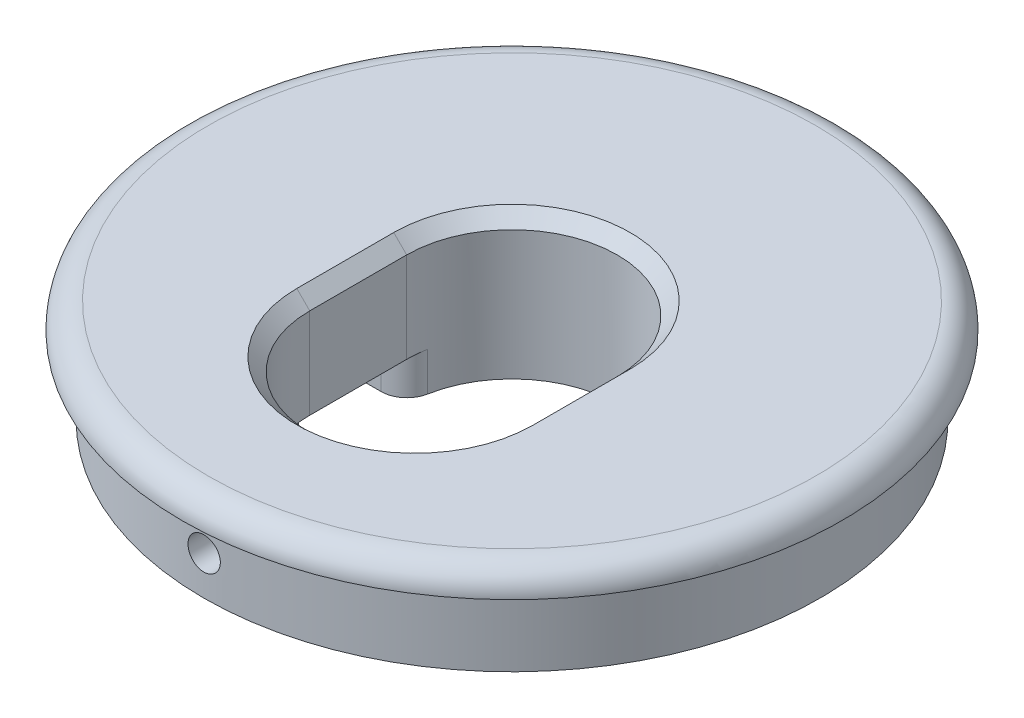
SolidWorks part; units mm, degrees
ref_plane "Front Plane" through (0, 0, 0) normal (0, 0, 1) x (1, 0, 0)
ref_plane "Top Plane" through (0, 0, 0) normal (0, 1, 0) x (1, 0, 0)
ref_plane "Right Plane" through (0, 0, 0) normal (1, 0, 0) x (0, 0, -1)
sketch "Sketch1" plane through (0, 0, 0) normal (0, 1, 0) x (1, 0, 0)
  circle A0 centre (0, 0) radius 23.85
  dimension "D1" = 47.7
extrude "Boss-Extrude1" add sketch "Sketch1" along normal blind 6
sketch "Sketch2" plane through (0, 6, 0) normal (0, 1, 0) x (1, 0, 0)
  circle A0 centre (0, 0) radius 25.5
  dimension "D1" = 51
extrude "Boss-Extrude2" add sketch "Sketch2" along normal blind 2
fillet "Fillet1" radius 2 1 edges at (0, 8, 25.5)
sketch "Sketch3" plane through (0, 8, 0) normal (0, 1, 0) x (1, 0, 0)
  line L0 (0, 0) -> (0, -7.5) construction
  line L1 (8.15, 0) -> (8.15, -7.5)
  line L2 (-8.15, 0) -> (-8.15, -7.5)
  arc A0 (8.15, 0) -> (-8.15, 0) centre (0, 0) ccw
  arc A1 (-8.15, -7.5) -> (8.15, -7.5) centre (0, -7.5) ccw
  point P3 (0, -3.75)
  dimension "D2" = 8.15
  dimension "D1" = 7.5
extrude "Cut-Extrude1" cut sketch "Sketch3" against normal through all
sketch "Sketch4" plane through (0, 0, 0) normal (0, -1, 0) x (1, 0, 0)
  line L0 (-12.15, 7.5) -> (-12.15, 0)
  line L1 (12.15, 0) -> (12.15, 7.5)
  line L2 (8.15, 0) -> (8.15, 7.5)
  line L3 (-8.15, 7.5) -> (-8.15, 0)
  line L4 (8.15, 0) -> (8.15, 7.5)
  line L5 (-8.15, 7.5) -> (-8.15, 0)
  arc A0 (12.15, 7.5) -> (-12.15, 7.5) centre (0, 7.5) ccw
  arc A1 (-12.15, 0) -> (12.15, 0) centre (0, 0) ccw
  arc A2 (-8.15, 0) -> (8.15, 0) centre (0, 0) ccw
  arc A3 (8.15, 7.5) -> (-8.15, 7.5) centre (0, 7.5) ccw
  arc A4 (-8.15, 0) -> (8.15, 0) centre (0, 0) ccw
  arc A5 (8.15, 7.5) -> (-8.15, 7.5) centre (0, 7.5) ccw
  dimension "D1" = 0
  dimension "D2" = 4
extrude "Boss-Extrude3" add sketch "Sketch4" along normal blind 3
sketch "Sketch5" plane through (0, -3, 0) normal (0, -1, 0) x (1, 0, 0)
  line L0 (0, 3.75) -> (0, 0) construction
  line L1 (14, 0.15) -> (-14, 0.15)
  line L2 (14, 0.15) -> (14, 7.35)
  line L3 (14, 7.35) -> (-14, 7.35)
  line L4 (-14, 0.15) -> (-14, 7.35)
  line L5 (14, 0.15) -> (-14, 7.35) construction
  line L6 (14, 7.35) -> (-14, 0.15) construction
  line L7 (0, 3.75) -> (8.15, 3.75) construction
  line L8 (8.15, 0) -> (8.15, 7.5) construction
  point P0 (0, 3.75)
  dimension "D1" = 7.2
  dimension "D2" = 28
extrude "Cut-Extrude2" cut sketch "Sketch5" against normal blind 3
sketch "Sketch6" plane through (0, 0, 0) normal (0, -1, 0) x (1, 0, 0)
  line L0 (0, 0) -> (0, 3.75) construction
  line L1 (0, 3.75) -> (-8.15, 3.75) construction
  line L2 (-8.15, 0.15) -> (-8.15, 7.35) construction
  line L3 (-8.15, 3.75) -> (-11, 3.75) construction
  line L4 (0, 3.75) -> (8.15, 3.75) construction
  line L5 (8.15, 7.35) -> (8.15, 0.15) construction
  line L6 (8.15, 3.75) -> (11, 3.75) construction
  circle A0 centre (-11, 3.75) radius 1.25
  circle A1 centre (11, 3.75) radius 1.25
  dimension "D2" = 2.5
  dimension "D1" = 22
extrude "Cut-Extrude3" cut sketch "Sketch6" against normal blind 5
fillet "Fillet2" radius 2 4 edges at (8.15, -1.5, 0.15) (8.15, -1.5, 7.35) (-8.15, -1.5, 0.15) (-8.15, -1.5, 7.35)
chamfer "Chamfer1" distance 1 angle 45 4 edges at (-8.15, 8, 3.75) (0, 8, 15.65) (8.15, 8, 3.75) (0, 8, -8.15)
ref_plane "Plane1" through (0, 3, 0) normal (0, -1, 0) x (-1, 0, 0)
sketch "Sketch7" plane through (0, 3, 0) normal (0, -1, 0) x (-1, 0, 0)
  line L0 (0, 0) -> (0, -17.5) construction
  line L1 (0, -25.5) -> (1.25, -25.5)
  line L2 (0, -25.5) -> (0, -17.5)
  line L3 (0, -17.5) -> (1.25, -17.5)
  line L4 (1.25, -25.5) -> (1.25, -17.5)
  circle A0 centre (0, 0) radius 25.5 construction
  dimension "D1" = 8
  dimension "D2" = 1.25
revolve "Cut-Revolve1" cut sketch "Sketch7" angle 360 about L0
